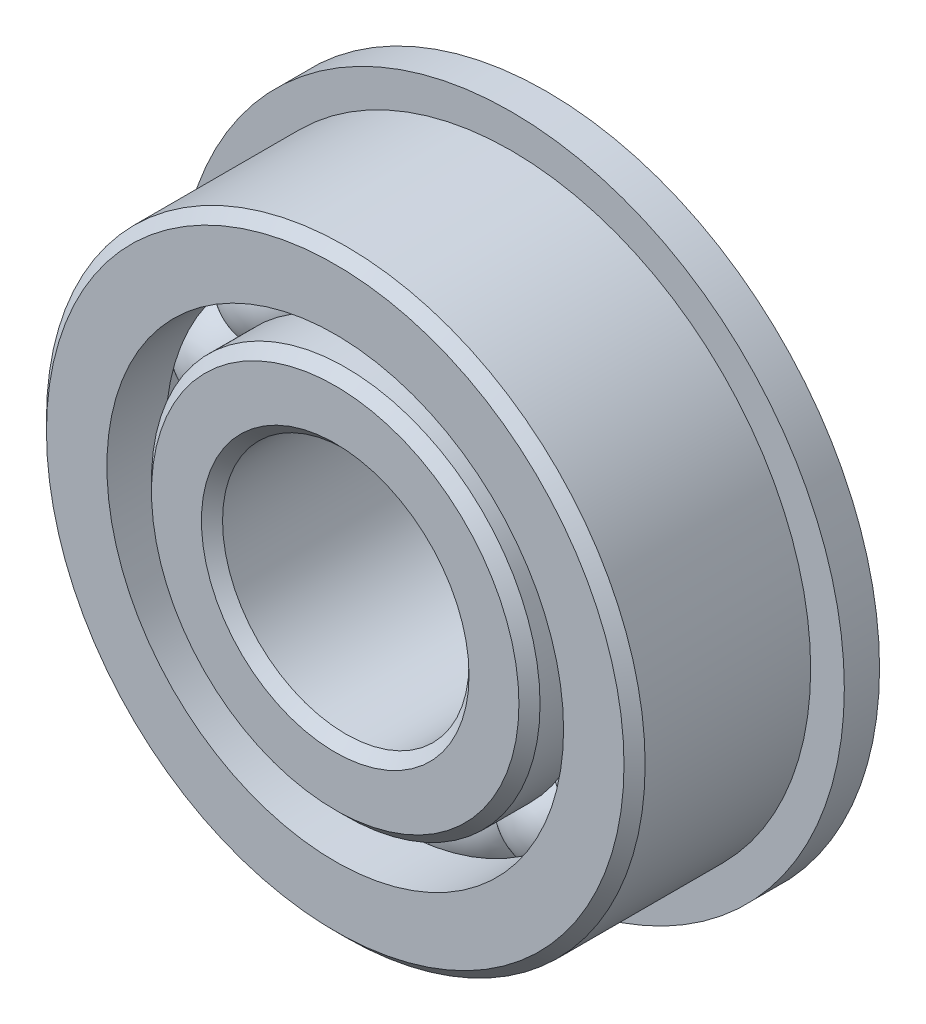
SolidWorks part; units mm, degrees
ref_plane "Front Plane" through (0, 0, 0) normal (0, 0, 1) x (1, 0, 0)
ref_plane "Top Plane" through (0, 0, 0) normal (0, 1, 0) x (1, 0, 0)
ref_plane "Right Plane" through (0, 0, 0) normal (1, 0, 0) x (0, 0, -1)
sketch "Sketch1" plane through (0, 0, 0) normal (1, 0, 0) x (0, 0, -1)
  line L0 (-4.7625, 0) -> (4.7625, 0) construction
  line L1 (0, 13.4937) -> (0, -13.4937) construction
  line L2 (4.2863, 13.4938) -> (-4.2863, 13.4937)
  line L3 (-4.2863, 13.4937) -> (-4.7625, 13.0175)
  line L4 (-4.7625, 13.0175) -> (-4.7625, 10.2926)
  line L5 (-4.7625, 10.2926) -> (-2.1167, 10.2926)
  line L6 (4.7625, 10.2926) -> (2.1167, 10.2926)
  line L7 (4.7625, 13.0175) -> (4.7625, 10.2926)
  line L8 (4.2863, 13.4938) -> (4.7625, 13.0175)
  line L9 (0, 13.4937) -> (0, 9.525) construction
  line L10 (0, 9.525) -> (0, 5.5562) construction
  arc A0 (-2.1167, 10.2926) -> (2.1167, 10.2926) centre (0, 9.525) cw
  point P14 (0, 5.5562)
  dimension "Width" = 9.525
  dimension "OD" = 26.9875
  dimension "D1" = 45
  dimension "D2" = 0.4763
  dimension "D3" = 4.2333
  dimension "D4" = 0.7676
revolve "Revolve1" add sketch "Sketch1" angle 360 about L0
sketch "Sketch3" plane through (0, 0, 0) normal (1, 0, 0) x (0, 0, -1)
  line L0 (-2.1167, 8.7574) -> (-4.7625, 8.7574) construction
  line L1 (-4.7625, 13.0175) -> (-4.7625, 10.2926) construction
  line L2 (-4.2863, 13.4937) -> (-4.7625, 13.0175) construction
  line L3 (-4.7625, 8.7574) -> (-4.7625, 6.0325) construction
  line L4 (-4.7625, 6.0325) -> (-4.7625, 8.2812)
  line L5 (-4.7625, 6.0325) -> (-4.2863, 5.5563)
  line L6 (-4.2863, 5.5563) -> (5.8737, 5.5563)
  line L7 (-4.7625, 13.0175) -> (-4.7625, -13.0175) construction
  line L8 (5.8737, 5.5563) -> (6.35, 6.0325)
  line L10 (6.35, 6.0325) -> (6.35, 8.7574) construction
  line L11 (6.35, 8.7574) -> (2.1167, 8.7574) construction
  line L12 (0, 13.4937) -> (0, -13.4937) construction
  line L13 (4.2863, 13.4938) -> (4.7625, 13.0175) construction
  line L14 (-4.7625, 8.2812) -> (-4.2863, 8.7574)
  line L15 (-4.2863, 8.7574) -> (-2.1167, 8.7574)
  line L16 (2.1167, 8.7574) -> (5.8737, 8.7574)
  line L17 (5.8737, 8.7574) -> (6.35, 8.2812)
  line L18 (6.35, 8.2812) -> (6.35, 6.0325)
  arc A1 (2.1167, 8.7574) -> (-2.1167, 8.7574) centre (0, 9.525) cw
  arc A2 (2.1167, 10.2926) -> (-2.1167, 10.2926) centre (0, 9.525) ccw construction
  dimension "D1" = 45
  dimension "Ring Wd" = 11.1125
revolve "Revolve3" add sketch "Sketch3" angle 360 about L0
sketch "Sketch4" plane through (0, 0, 0) normal (1, 0, 0) x (0, 0, -1)
  line L0 (-2.2515, 9.525) -> (2.2515, 9.525)
  arc A2 (-2.2515, 9.525) -> (2.2515, 9.525) centre (0, 9.525) cw
  arc A3 (2.1167, 10.2926) -> (-2.1167, 10.2926) centre (0, 9.525) ccw construction
revolve "Revolve4" add sketch "Sketch4" angle 360 about L0
ref_axis "Axis1" through (0, 0, -4.7625) along (0, 0, 1)
pattern_circular "CirPattern1" count 15 every 24 about axis through (0, 0, -4.7625) along (0, 0, 1) of bodies 104
sketch "Sketch5" plane through (0, 0, 0) normal (1, 0, 0) x (0, 0, -1)
  line L0 (-4.7625, 10.2926) -> (-2.1167, 10.2926) construction
  line L1 (-4.5244, 10.2926) -> (-2.2515, 10.2926)
  line L2 (-4.5244, 10.2926) -> (-4.5244, 8.7574)
  line L3 (-4.5244, 8.7574) -> (-2.2515, 8.7574)
  line L4 (-2.2515, 10.2926) -> (-2.2515, 8.7574)
  line L5 (-2.1167, 8.7574) -> (-4.7625, 8.7574) construction
  line L6 (4.7625, 10.2926) -> (2.1167, 10.2926) construction
  line L7 (4.5244, 10.2926) -> (2.2515, 10.2926)
  line L8 (4.5244, 10.2926) -> (4.5244, 8.7574)
  line L9 (4.5244, 8.7574) -> (2.2515, 8.7574)
  line L10 (2.2515, 10.2926) -> (2.2515, 8.7574)
  line L11 (6.35, 8.7574) -> (2.1167, 8.7574) construction
  line L12 (-4.2863, 13.4937) -> (-4.7625, 13.0175) construction
  point P18 (-4.5244, 13.2556)
revolve "Revolve5" [suppressed] add sketch "Sketch5" angle 360 about L0
sketch "Sketch6" plane through (0, 0, 0) normal (1, 0, 0) x (0, 0, -1)
  line L1 (4.7625, 10.2926) -> (3.175, 10.2926)
  line L2 (4.7625, 10.2926) -> (4.7625, 15.0114)
  line L3 (4.7625, 15.0114) -> (3.175, 15.0114)
  line L4 (3.175, 10.2926) -> (3.175, 15.0114)
  line L5 (4.7625, 0) -> (-4.7625, 0) construction
  dimension "Flange OD" = 30.0228
  dimension "Th" = 1.5875
revolve "Revolve6" add sketch "Sketch6" angle 360 about L5
equation "\"D2@Sketch1\" = \"Width@Sketch1\"*.05"
equation "\"D3@Sketch1\" = \"Width@Sketch1\"/2.25"
equation "\"D4@Sketch1\" = (((\"OD@Sketch1\"-\"Width@Sketch1\")/2)/3.25)/3.5"
equation "\"D2@CirPattern1\" = 360/\"Balls@CirPattern1\""
